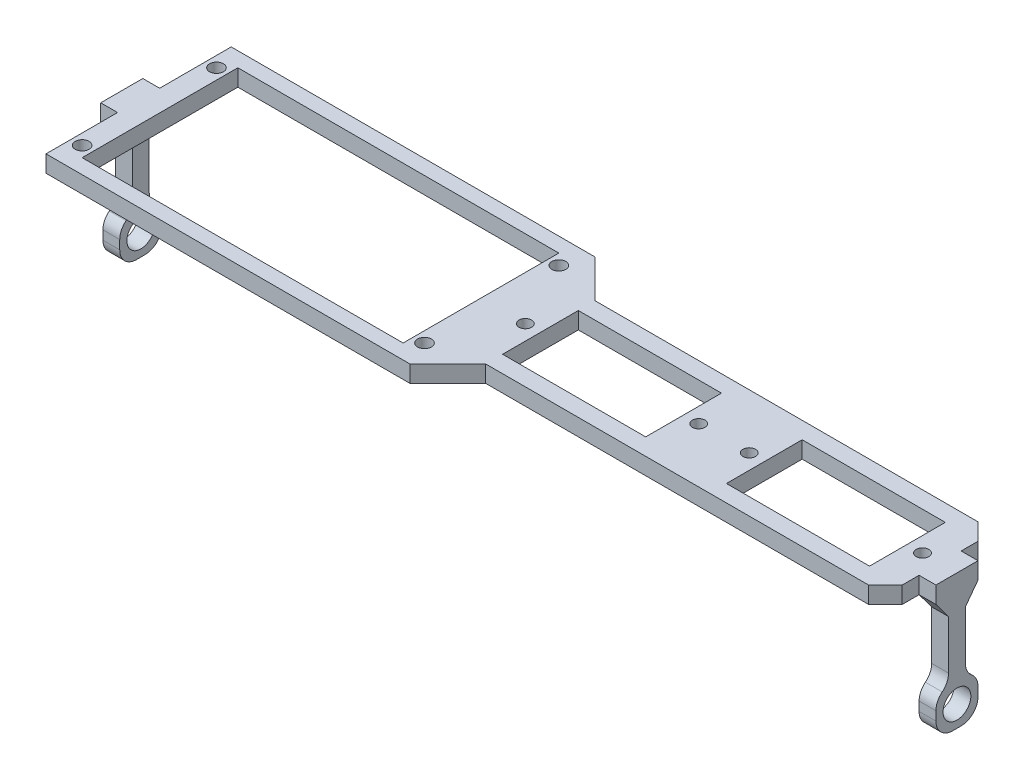
SolidWorks part; units mm, degrees
ref_plane "Plan de face" through (0, 0, 0) normal (0, 0, 1) x (1, 0, 0)
ref_plane "Plan de dessus" through (0, 0, 0) normal (0, 1, 0) x (1, 0, 0)
ref_plane "Plan de droite" through (0, 0, 0) normal (1, 0, 0) x (0, 0, -1)
sketch "Esquisse1" plane through (0, 0, 0) normal (0, 1, 0) x (1, 0, 0)
  line L0 (9.6088, 14.324) -> (9.6088, -7.676) construction
  line L1 (-11.9962, 14.324) -> (31.2138, 14.324)
  line L2 (-11.9962, 14.324) -> (-11.9962, -7.676)
  line L3 (-11.9962, -7.676) -> (31.2138, -7.676)
  line L4 (31.2138, 14.324) -> (31.2138, -7.676)
  line L5 (-11.9962, 5.824) -> (-13.9962, 5.824)
  line L6 (-11.9962, 5.824) -> (-11.9962, 0.824)
  line L7 (-11.9962, 0.824) -> (-13.9962, 0.824)
  line L8 (-13.9962, 5.824) -> (-13.9962, 0.824)
  line L9 (-9.4562, 3.324) -> (28.6738, 3.324) construction
  line L10 (28.6738, -5.926) -> (-9.4562, -5.926)
  line L11 (28.6738, -5.926) -> (28.6738, 12.574)
  line L12 (28.6738, 12.574) -> (-9.4562, 12.574)
  line L13 (-9.4562, -5.926) -> (-9.4562, 12.574)
  line L14 (28.6738, -5.926) -> (-9.4562, 12.574) construction
  line L15 (28.6738, 12.574) -> (-9.4562, -5.926) construction
  line L16 (35.7388, -3.176) -> (83.2138, -3.176)
  line L17 (52.7388, -1.176) -> (35.7388, -1.176)
  line L18 (52.7388, -1.176) -> (52.7388, 7.824)
  line L19 (52.7388, 7.824) -> (35.7388, 7.824)
  line L20 (35.7388, -1.176) -> (35.7388, 7.824)
  line L21 (52.7388, -1.176) -> (35.7388, 7.824) construction
  line L22 (52.7388, 7.824) -> (35.7388, -1.176) construction
  line L23 (35.7388, 9.824) -> (83.2138, 9.824)
  line L24 (31.2138, -7.676) -> (35.7388, -3.176)
  line L25 (31.2138, 14.324) -> (35.7388, 9.824)
  line L26 (44.2388, 7.824) -> (44.2388, -1.176) construction
  line L27 (57.5338, 9.824) -> (57.5338, -3.176) construction
  line L36 (83.2138, 9.824) -> (83.2138, -3.176)
  line L37 (79.3288, -1.176) -> (79.3288, 7.824)
  line L38 (83.2138, 5.824) -> (85.2138, 5.824)
  line L39 (83.2138, 5.824) -> (83.2138, 0.824)
  line L40 (83.2138, 0.824) -> (85.2138, 0.824)
  line L41 (85.2138, 5.824) -> (85.2138, 0.824)
  line L42 (62.3288, -1.176) -> (79.3288, -1.176)
  line L43 (62.3288, -1.176) -> (62.3288, 7.824)
  line L44 (62.3288, 7.824) -> (79.3288, 7.824)
  circle A0 centre (-10.7262, 11.304) radius 0.825
  circle A1 centre (29.9438, 11.304) radius 0.825
  circle A2 centre (29.9438, -4.656) radius 0.825
  circle A3 centre (-10.7262, -4.656) radius 0.825
  circle A4 centre (33.9438, 3.324) radius 0.75
  circle A5 centre (54.5338, 3.324) radius 0.75
  circle A6 centre (60.5338, 3.324) radius 0.75
  circle A7 centre (81.1238, 3.324) radius 0.75
  point P8 (-13.9962, 3.324)
  point P9 (-11.9962, 3.324)
  point P12 (9.6088, 3.324)
  point P13 (9.6088, 3.324)
  point P28 (44.2388, 3.324)
  point P37 (33.6388, 3.324)
  point P39 (33.9438, 3.324)
  point P42 (33.6388, 3.324)
  point P46 (0, 0)
  point P49 (54.5338, 3.324)
  point P50 (0, 0)
  point P51 (0, 0)
  point P58 (83.2138, 3.324)
  point P59 (85.2138, 3.324)
  point P60 (33.6388, 3.324)
  dimension "D8" = 1.65
  dimension "D16" = 1.5
  dimension "D1" = 22
  dimension "D2" = 43.21
  dimension "D3" = 5
  dimension "D4" = 2
  dimension "D5" = 2.54
  dimension "D6" = 2.54
  dimension "D7" = 18.5
  dimension "D9" = 1.27
  dimension "D10" = 1.27
  dimension "D11" = 17
  dimension "D12" = 9
  dimension "D13" = 4
  dimension "D14" = 2
  dimension "D15" = 2
  dimension "D17" = 52
  dimension "D18" = 3
  dimension "D19" = 5
  dimension "D20" = 2
  dimension "D21" = 10.295
extrude "Boss.-Extru.1" add sketch "Esquisse1" along normal blind 2 contours L4 L1 L2 L3 A1 A0 L10 L13 L12 L11 A2 A3 | L36 L23 L25 L4 L24 L16 A4 L17 L20 L19 L18 A6 | L41 L38 L36 L40 | L5 L8 L7 L2 region at (9.6088, 0, -13.8391) region at (55.6513, 0, -3.324) region at (-12.9962, 0, -3.324) region at (84.2138, 0, -3.324)
chamfer "Chanfrein1" distance 2 angle 45 2 edges at (83.2138, 1, 3.176) (83.2138, 1, -9.824)
sketch "Esquisse2" plane through (85.2138, 0, 0) normal (1, 0, 0) x (0, 0, -1)
  line L0 (3.324, -14) -> (3.324, -11.5) construction
  line L1 (0.824, 0) -> (5.824, 0)
  line L2 (0.824, 0) -> (0.824, -14)
  line L3 (0.824, -14) -> (5.824, -14)
  line L4 (5.824, 0) -> (5.824, -14)
  line L5 (3.324, -11.5) -> (0.824, -11.5) construction
  line L6 (3.324, -11.5) -> (3.324, -9) construction
  line L7 (0.824, -9) -> (2.324, -9)
  line L8 (2.324, -9) -> (2.324, -2)
  line L9 (2.324, -2) -> (0.824, 0)
  line L10 (5.824, -9) -> (4.324, -9)
  line L11 (4.324, -9) -> (4.324, -2)
  line L12 (4.324, -2) -> (5.824, 0)
  circle A0 centre (3.324, -11.5) radius 1.65
  point P5 (0, 0)
  point P13 (3.324, -11.5)
  point P15 (0, 0)
  point P20 (0, 0)
  line M7 (0.824, 0) -> (5.824, 0)
  dimension "D2" = 3.3
  dimension "D1" = 9
  dimension "D3" = 2
  dimension "D5" = 1.5
extrude "Boss.-Extru.2" add sketch "Esquisse2" against normal blind 2 contours L9 L8 L7 L2 L3 L4 A0 M7 region at (85.2138, -7.2674, -3.324)
mirror "Symétrie1" about plane through (35.7388, 2, 0) normal (-1, 0, 0) of "Boss.-Extru.2"
fillet "Congé1" radius 2 8 edges at (84.2138, -14, -5.824) (84.2138, -14, -0.824) (84.2138, -9, -5.824) (84.2138, -9, -0.824) (-12.7362, -14, -5.824) (-12.7362, -9, -5.824) (-12.7362, -9, -0.824) (-12.7362, -14, -0.824)
fillet "Congé4" radius 2 4 edges at (-12.7362, -9, -4.324) (84.2138, -9, -4.324) (84.2138, -9, -2.324) (-12.7362, -9, -2.324)
